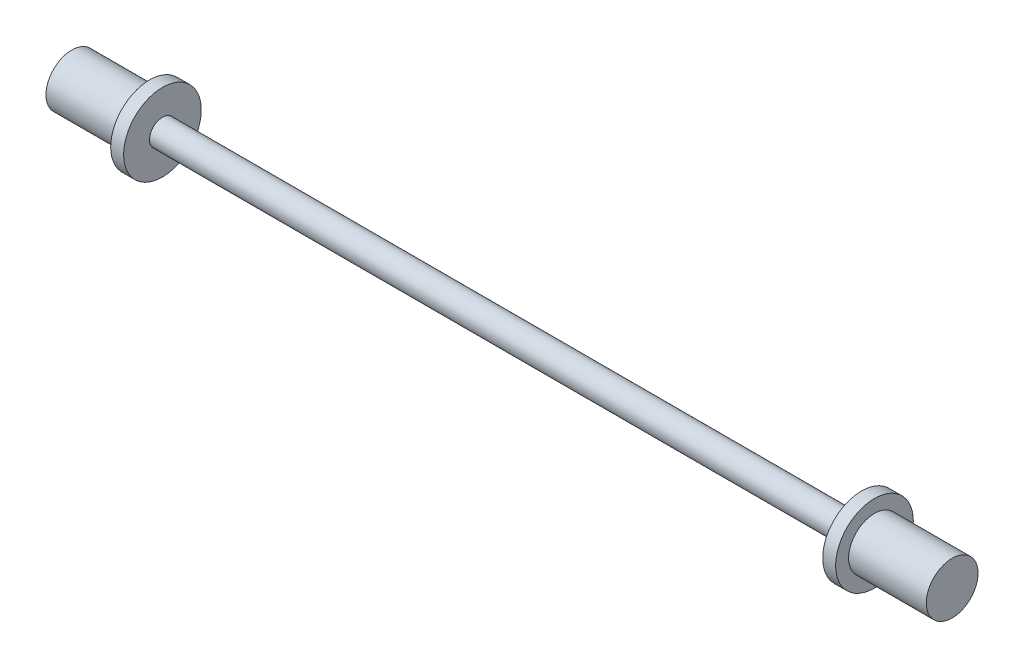
SolidWorks part; units mm, degrees
ref_plane "Front Plane" through (0, 0, 0) normal (0, 0, 1) x (1, 0, 0)
ref_plane "Top Plane" through (0, 0, 0) normal (0, 1, 0) x (1, 0, 0)
ref_plane "Right Plane" through (0, 0, 0) normal (1, 0, 0) x (0, 0, -1)
sketch "Sketch2" plane through (0, 0, 0) normal (1, 0, 0) x (0, 0, -1)
  circle A0 centre (0, 0) radius 6.35
  dimension "D1" = 12.7
extrude "Boss-Extrude1" add sketch "Sketch2" along normal blind 171.45 and the other way blind 171.45
sketch "Sketch3" plane through (171.45, 0, 0) normal (1, 0, 0) x (0, 0, -1)
  circle A0 centre (0, 0) radius 19.05
  dimension "D1" = 38.1
extrude "Boss-Extrude2" add sketch "Sketch3" along normal blind 6.35
sketch "Sketch7" plane through (-171.45, 0, 0) normal (-1, 0, 0) x (0, 0, 1)
  circle A0 centre (0, 0) radius 19.05 construction
  circle A3 centre (0, 0) radius 19.05
extrude "Boss-Extrude4" add sketch "Sketch7" along normal blind 6.35
sketch "Sketch9" plane through (-177.8, 0, 0) normal (-1, 0, 0) x (0, 0, 1)
  circle A0 centre (0, 0) radius 12.7
  dimension "D1" = 25.4
extrude "Boss-Extrude6" add sketch "Sketch9" along normal blind 38.1
sketch "Sketch10" plane through (177.8, 0, 0) normal (1, 0, 0) x (0, 0, -1)
  circle A0 centre (0, 0) radius 12.7 construction
  circle A1 centre (0, 0) radius 12.7
extrude "Boss-Extrude7" add sketch "Sketch10" along normal blind 38.1
